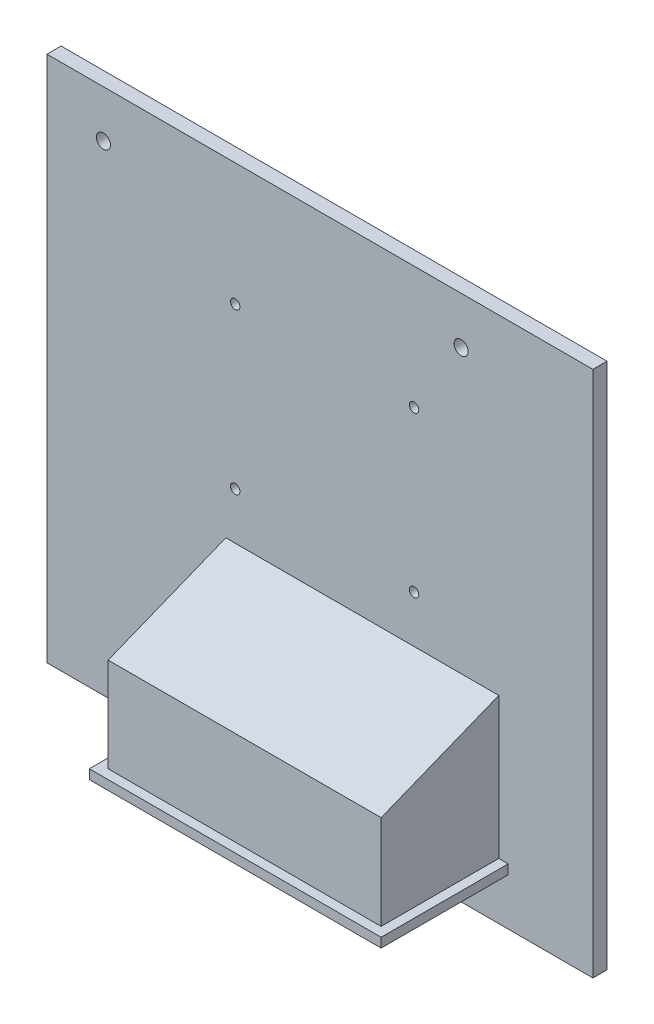
SolidWorks part; units mm, degrees
ref_plane "Front" through (0, 0, 0) normal (0, 0, 1) x (1, 0, 0)
ref_plane "Top" through (0, 0, 0) normal (0, 1, 0) x (1, 0, 0)
ref_plane "Right" through (0, 0, 0) normal (1, 0, 0) x (0, 0, -1)
sketch "Sketch1" plane through (0, 0, 0) normal (0, 0, 1) x (1, 0, 0)
  line L1 (-58, -56) -> (58, -56)
  line L2 (-58, -56) -> (-58, 56)
  line L3 (-58, 56) -> (58, 56)
  line L4 (58, -56) -> (58, 56)
  line L5 (-58, -56) -> (58, 56) construction
  line L6 (-58, 56) -> (58, -56) construction
  point P0 (0, 0)
  dimension "D1" = 112
  dimension "D2" = 116
extrude "Boss-Extrude1" add sketch "Sketch1" along normal blind 3
sketch "Sketch2" plane through (0, 0, 3) normal (0, 0, 1) x (1, 0, 0)
  line L0 (-58, -56) -> (58, -56) construction
  line L1 (-20, -48) -> (38, -48)
  line L2 (-20, -48) -> (-20, -14)
  line L3 (-20, -14) -> (38, -14)
  line L4 (38, -48) -> (38, -14)
  line L5 (-20, -48) -> (38, -14) construction
  line L6 (-20, -14) -> (38, -48) construction
  line L7 (58, -56) -> (58, 56) construction
  point P0 (9, -31)
  dimension "D1" = 34
  dimension "D2" = 58
  dimension "D3" = 8
  dimension "D4" = 20
extrude "Boss-Extrude2" add sketch "Sketch2" along normal blind 25
chamfer "Chamfer1" distance 25 distance2 10 1 edges at (9, -14, 28) first distance on face at (9, -14, 15.5)
ref_plane "Plane1" through (0, -43, 0) normal (0, -1, 0) x (-1, 0, 0)
ref_plane "Plane2" through (0, -46, 0) normal (0, -1, 0) x (-1, 0, 0)
sketch "Sketch4" plane through (0, -46, 0) normal (0, -1, 0) x (-1, 0, 0)
  line L4 (20, -3) -> (-38, -3)
  line L5 (-38, -3) -> (-38, -28)
  line L6 (-38, -28) -> (20, -28)
  line L7 (20, -28) -> (20, -3)
  line L8 (22, -3) -> (-40, -3)
  line L9 (-38, -3) -> (-38, -28)
  line L10 (-38, -28) -> (20, -28)
  line L11 (20, -28) -> (20, -3)
  line L16 (22, -1) -> (-40, -1)
  line L17 (-40, -1) -> (-40, -30)
  line L18 (-40, -30) -> (22, -30)
  line L19 (22, -30) -> (22, -1)
  line L20 (22, -1) -> (-40, -1)
  line L21 (-40, -1) -> (-40, -30)
  line L22 (-40, -30) -> (22, -30)
  line L23 (22, -30) -> (22, -1)
  dimension "D1" = 0
  dimension "D2" = 2
extrude "Boss-Extrude4" add sketch "Sketch4" against normal blind 2 contours L22 L23 L8 L11 L10 L9 L21 region at (-21, -46, 3.6762)
sketch "Sketch5" plane through (0, 0, 3) normal (0, 0, 1) x (1, 0, 0)
  line L0 (58, 56) -> (-58, 56) construction
  line L1 (-58, 56) -> (-58, -56) construction
  line L2 (58, -56) -> (58, 56) construction
  line L3 (-58, -56) -> (58, -56) construction
  circle A0 centre (-46, 46) radius 1.5
  circle A1 centre (30, 46) radius 1.5
  circle A2 centre (-36, -46) radius 1.5
  dimension "D1" = 3
  dimension "D2" = 3
  dimension "D3" = 3
  dimension "D6" = 28
  dimension "D8" = 22
  dimension "D4" = 10
  dimension "D5" = 12
  dimension "D7" = 10
extrude "Cut-Extrude1" cut sketch "Sketch5" against normal up to next
sketch "Sketch6" plane through (0, 0, 3) normal (0, 0, 1) x (1, 0, 0)
  line L0 (-20, -14) -> (-20, -44) construction
  line L1 (-20, 32) -> (22, 32)
  line L2 (-20, 32) -> (-20, 28)
  line L3 (-20, 28) -> (22, 28)
  line L4 (22, 32) -> (22, 28)
  line L5 (-20, 32) -> (22, 28) construction
  line L6 (-20, 28) -> (22, 32) construction
  line L7 (-20, -2) -> (22, -2)
  line L8 (-20, -2) -> (-20, -6)
  line L9 (-20, -6) -> (22, -6)
  line L10 (22, -2) -> (22, -6)
  line L11 (-20, -2) -> (22, -6) construction
  line L12 (-20, -6) -> (22, -2) construction
  line L13 (-16, 28) -> (-12, 28)
  line L14 (-16, 28) -> (-16, -2)
  line L15 (-16, -2) -> (-12, -2)
  line L16 (-12, 28) -> (-12, -2)
  line L17 (-16, 28) -> (-12, -2) construction
  line L18 (-16, -2) -> (-12, 28) construction
  line L19 (14, 28) -> (18, 28)
  line L20 (14, 28) -> (14, -2)
  line L21 (14, -2) -> (18, -2)
  line L22 (18, 28) -> (18, -2)
  line L23 (14, 28) -> (18, -2) construction
  line L24 (14, -2) -> (18, 28) construction
  line L25 (38, -14) -> (-20, -14) construction
  circle A0 centre (-18, 30) radius 1
  circle A1 centre (20, 30) radius 1
  circle A2 centre (20, -4) radius 1
  circle A3 centre (-18, -4) radius 1
  point P0 (1, 30)
  point P5 (1, -4)
  point P15 (-14, 13)
  point P19 (16, 13)
  dimension "D8" = 2
  dimension "D10" = 2
  dimension "D11" = 2
  dimension "D12" = 2
  dimension "D13" = 2
  dimension "D14" = 2
  dimension "D1" = 4
  dimension "D2" = 42
  dimension "D3" = 4
  dimension "D4" = 42
  dimension "D5" = 30
  dimension "D6" = 4
  dimension "D7" = 4
  dimension "D9" = 2
  dimension "D15" = 2
  dimension "D16" = 4
  dimension "D17" = 4
  dimension "D18" = 2
  dimension "D19" = 10
extrude "Cut-Extrude2" cut sketch "Sketch6" against normal up to next contours A0 | A1 | A3 | A2 region at (-18, 30, 3) region at (20, 30, 3) region at (20, -4, 3) region at (-18, -4, 3)
